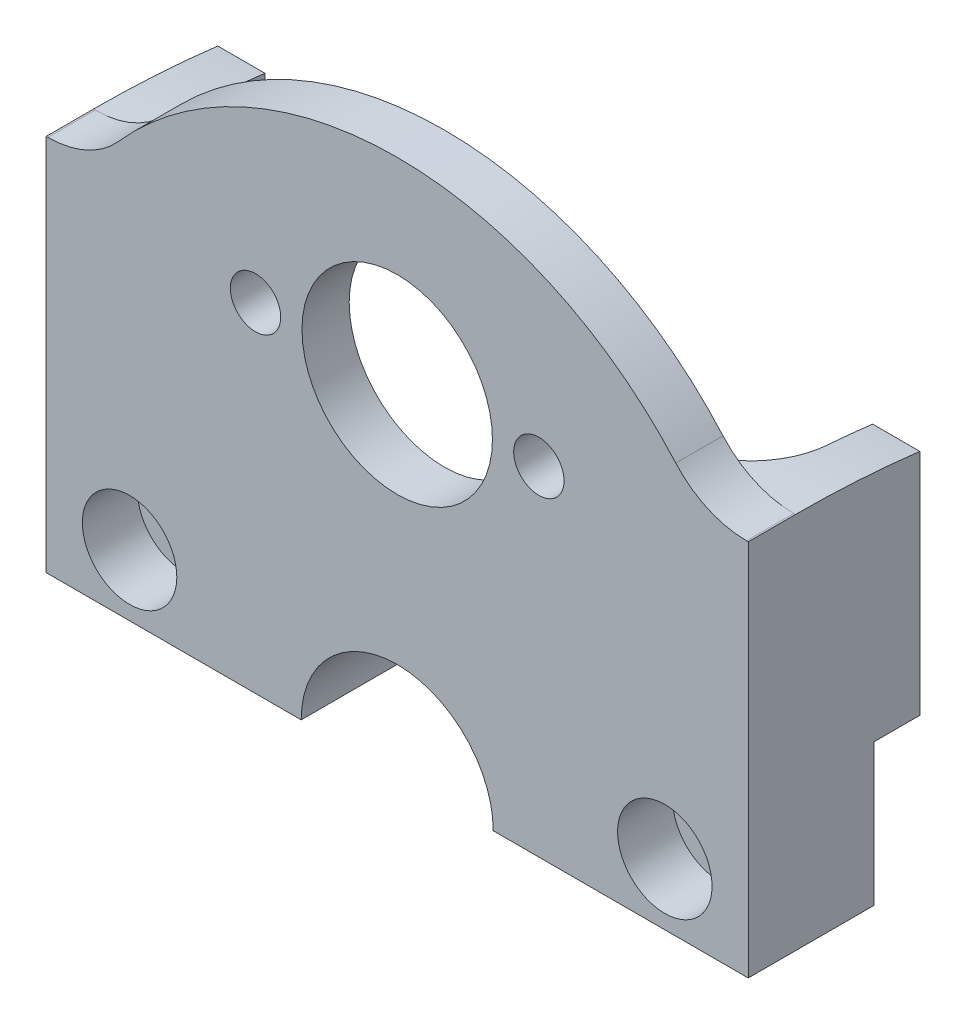
SolidWorks part; units mm, degrees
material "ABS"
ref_plane "正面" through (0, 0, 0) normal (0, 0, 1) x (1, 0, 0)
ref_plane "平面" through (0, 0, 0) normal (0, 1, 0) x (1, 0, 0)
ref_plane "右側面" through (0, 0, 0) normal (1, 0, 0) x (0, 0, -1)
sketch "ｽｹｯﾁ2" plane through (0, 0, 0) normal (0, 0, 1) x (1, 0, 0)
  line L0 (0, -18.7) -> (0, 18.7) construction
  line L1 (-9, 36.4) -> (9, 36.4) construction
  line L2 (0, 17) -> (0, 0) construction
  line L3 (-22.3, 23.9) -> (-22.3, 14.9)
  line L4 (-22.3, 48.9) -> (22.3, 48.9) construction
  line L5 (-22.3, 48.9) -> (-22.3, 23.9) construction
  line L6 (-22.3, 23.9) -> (22.3, 23.9)
  line L7 (22.3, 48.9) -> (22.3, 23.9) construction
  line L8 (-22.3, 48.9) -> (22.3, 23.9) construction
  line L9 (-22.3, 23.9) -> (22.3, 48.9) construction
  line L10 (-22.3, 14.9) -> (22.3, 14.9)
  line L11 (22.3, 14.9) -> (22.3, 23.9)
  line L12 (-22.3, 38.9) -> (-22.3, 23.9)
  line L13 (22.3, 38.9) -> (22.3, 23.9)
  line L14 (-22.3, 38.9) -> (-19.3, 38.9)
  line L15 (19.3, 38.9) -> (22.3, 38.9)
  line L16 (-17, 18.8) -> (17, 18.8) construction
  line L17 (-25, -15) -> (25, -15) construction
  line L18 (-25, -15) -> (-25, 23.9) construction
  line L19 (-25, 23.9) -> (25, 23.9) construction
  line L20 (25, -15) -> (25, 23.9) construction
  line L21 (-25, -15) -> (25, 23.9) construction
  line L22 (-25, 23.9) -> (25, -15) construction
  circle A0 centre (0, 0) radius 21.5 construction
  circle A1 centre (0, 0) radius 10.25 construction
  circle A2 centre (0, 36.4) radius 6.05
  circle A3 centre (-9, 36.4) radius 1.6
  circle A4 centre (9, 36.4) radius 1.6
  circle A6 centre (0, 0) radius 17 construction
  circle A9 centre (0, 17) radius 4 construction
  circle A10 centre (0, 36.4) radius 12.5 construction
  arc A11 (-6.1, 14.9) -> (6.1, 14.9) centre (0, 14.9) cw
  arc A12 (-19.3, 38.9) -> (19.3, 38.9) centre (0, 25.2755) cw
  circle A13 centre (-17, 18.8) radius 1.6
  circle A14 centre (17, 18.8) radius 1.6
  point P10 (0, 36.4)
  point P14 (0, 0)
  point P19 (0, 0)
  point P33 (0, 18.8)
  dimension "D1" = 12.1
  dimension "D2" = 3.2
  dimension "D3" = 43
  dimension "D4" = 34
  dimension "D5" = 20.5
  dimension "D8" = 25
  dimension "D12" = 8
  dimension "D6" = 36.4
  dimension "D7" = 18
  dimension "D10" = 25
  dimension "D11" = 9
  dimension "D13" = 15
  dimension "D14" = 3
  dimension "D15" = 50
  dimension "D9" = 2.7
  dimension "D16" = 8
  dimension "D17" = 5.1
  dimension "D18" = 15
  dimension "D19" = 38.9
extrude "ﾎﾞｽ - 押し出し1" add sketch "ｽｹｯﾁ2" against normal blind 3 contours L7 L4 L5 L6 A4 A3 A2 region at (-21.7887, 31.4, 0)
extrude "ﾎﾞｽ - 押し出し2" add sketch "ｽｹｯﾁ2<3>" against normal blind 8 contours L10 L11 L6 L3 region at (0, 23.445, 0)
sketch "ｽｹｯﾁ2<3>" plane through (0, 0, 0) normal (0, 0, 1) x (1, 0, 0) same geometry as "ｽｹｯﾁ2"
sketch "ｽｹｯﾁ3" plane through (-22.3, 0, 0) normal (-1, 0, 0) x (0, 0, 1)
  line L0 (-8, 23.9) -> (-10.9, 23.9)
  line L1 (-8, 23.9) -> (-43, 23.9) construction
  line L2 (-43, 23.9) -> (-43, 20.1209) construction
  line L3 (-3, 38.9) -> (0, 38.9) construction
  line L4 (-43, 16.1209) -> (-10.9, 16.1209)
  line L5 (-8, 23.9) -> (-3, 23.9)
  line L6 (-3, 23.9) -> (-3, 38.9)
  line L7 (-10.9, 16.1209) -> (-10.9, 23.9)
  arc A1 (-43, 16.1209) -> (-45.6008, 23.16) centre (-43, 20.1209) cw
  arc A2 (-45.6008, 23.16) -> (-3, 38.9) centre (-3, -26.62) cw
  circle A3 centre (-43, 20.1209) radius 1.65
  dimension "D2" = 3.3
  dimension "D3" = 4
  dimension "D1" = 2.9
  dimension "D4" = 35
  dimension "D5" = 3.7791
extrude "ﾎﾞｽ - 押し出し4" add sketch "ｽｹｯﾁ3" against normal blind 3
mirror "ﾐﾗｰ11" about plane through (0, 0, 0) normal (1, 0, 0) of "ﾎﾞｽ - 押し出し4"
fillet "ﾌｨﾚｯﾄ8" [suppressed] radius 3
fillet "ﾌｨﾚｯﾄ9" [suppressed] radius 3
sketch "ｽｹｯﾁ5" plane through (0, 0, 0) normal (0, 0, 1) x (1, 0, 0)
  circle A0 centre (-17, 18.8) radius 3
  circle A1 centre (17, 18.8) radius 3
  dimension "D1" = 6
extrude "ｶｯﾄ - 押し出し1" cut sketch "ｽｹｯﾁ5" against normal blind 3.5
sketch "ｽｹｯﾁ6" plane through (-22.3, 0, 0) normal (-1, 0, 0) x (0, 0, 1)
  line L0 (-43, 16.1209) -> (-10.9, 16.1209) construction
  line L1 (-66.2053, 67.203) -> (-10.9, 67.203)
  line L2 (-66.2053, 67.203) -> (-66.2053, 16.1209)
  line L3 (-66.2053, 16.1209) -> (-10.9, 16.1209)
  line L4 (-10.9, 67.203) -> (-10.9, 16.1209)
  line L5 (-66.2053, 67.203) -> (-10.9, 16.1209) construction
  line L6 (-66.2053, 16.1209) -> (-10.9, 67.203) construction
  point P0 (-38.5526, 41.6619)
extrude "ｶｯﾄ - 押し出し2" cut sketch "ｽｹｯﾁ6" against normal through all
fillet "ﾌｨﾚｯﾄ10" radius 6 2 edges at (19.3, 38.9, -1.5) (-19.3, 38.9, -1.5)
fillet "ﾌｨﾚｯﾄ11" radius 5 2 edges at (19.3, 31.4, -3) (-19.3, 31.4, -3)
equation "\"D6@ｽｹｯﾁ2\"=(65+26)*0.8/2"
equation "\"D5@ｽｹｯﾁ3\"=39/2-20*sin(50)-0.4"
